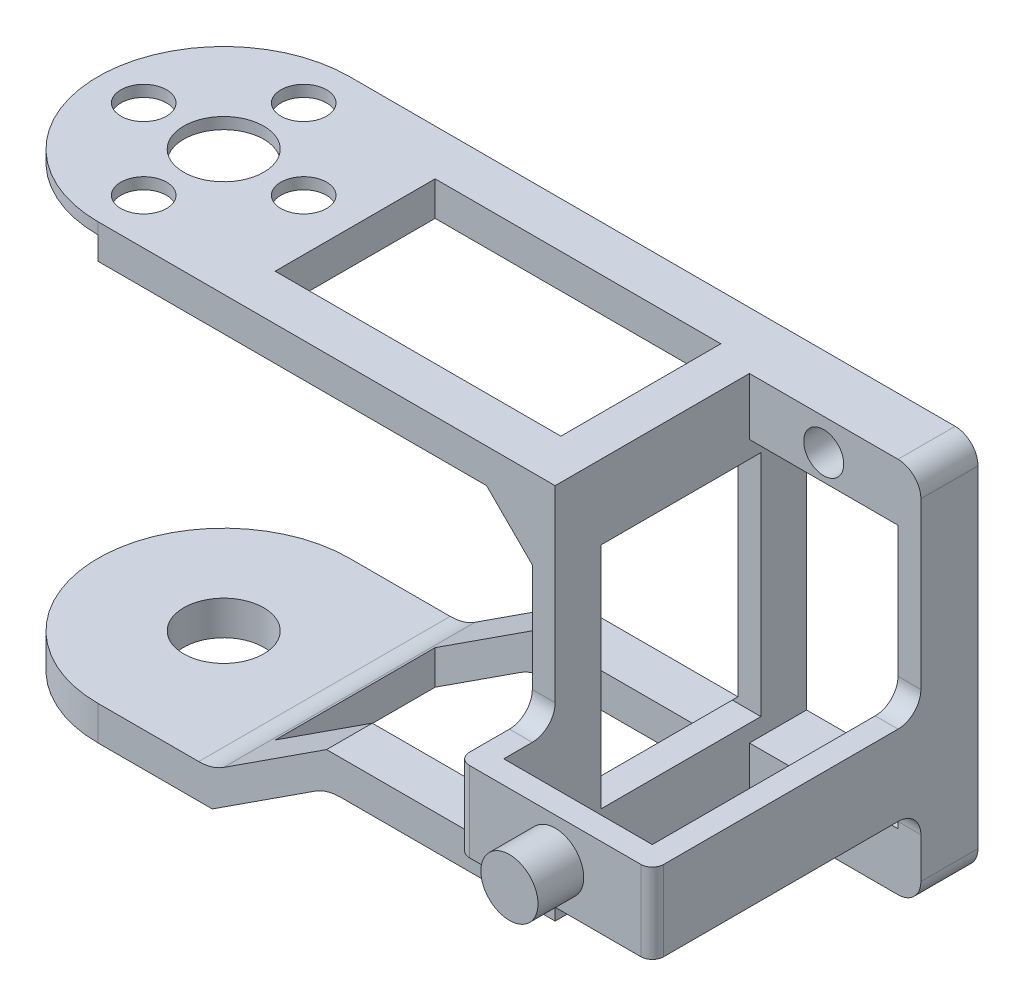
SolidWorks part; units mm, degrees
ref_plane "前视基准面" through (0, 0, 0) normal (0, 0, 1) x (1, 0, 0)
ref_plane "上视基准面" through (0, 0, 0) normal (0, 1, 0) x (1, 0, 0)
ref_plane "右视基准面" through (0, 0, 0) normal (1, 0, 0) x (0, 0, -1)
sketch "草图1" plane through (0, 0, 0) normal (0, 1, 0) x (1, 0, 0)
  line L0 (-11, 0) -> (11, 0) construction
  line L1 (0, -11) -> (0, 11) construction
  circle A1 centre (0, 0) radius 3
  circle A2 centre (-7, 0) radius 2
  circle A6 centre (0, 7) radius 2
  circle A7 centre (7, 0) radius 2
  circle A8 centre (0, -7) radius 2
  point P18 (0, 0)
  point P19 (0.1023, 0.1023)
  dimension "D1" = 7
  dimension "D2" = 6
  dimension "D3" = 4
  dimension "D4" = 4
sketch "草图2" plane through (0, 0, 0) normal (0, 1, 0) x (1, 0, 0)
  line L0 (0, -11) -> (0, 11) construction
  line L1 (0, 0) -> (67.4561, 0) construction
  line L2 (0, 11) -> (40, 11)
  line L3 (40, 11) -> (40, -11)
  line L4 (40, -11) -> (0, -11)
  arc A0 (0, -11) -> (0, 11) centre (0, 0) cw
  point P5 (40, 0)
  dimension "D1" = 11
  dimension "D4" = 40
  dimension "D3" = 11
  dimension "D2" = 11
extrude "凸台-拉伸1" add sketch "草图2" along normal blind 3
sketch "草图3" plane through (0, 0, 0) normal (0, -1, 0) x (-1, 0, 0)
  circle A0 centre (0, 0) radius 11
  dimension "D1" = 22
extrude "切除-拉伸1" cut sketch "草图3" against normal blind 2 contours A0
extrude "切除-拉伸2" cut sketch "草图1" against normal through all and the other way blind 20
ref_plane "基准面1" through (0, -33.5, 0) normal (0, -1, 0) x (-1, 0, 0)
sketch "草图4" plane through (0, -33.5, 0) normal (0, -1, 0) x (-1, 0, 0)
  line L0 (0, 0.1404) -> (0, 50000.1404) construction
  line L1 (0, 0) -> (50000, 0) construction
  line L2 (0, 11) -> (-10, 11)
  line L4 (-10, 11) -> (-10, -11)
  line L5 (-10, -11) -> (0, -11)
  line L6 (0, -11) -> (-40, -11) construction
  arc A1 (0, 11) -> (0, -11) centre (0, 0) cw
  point P0 (0, 25000.1404)
  point P1 (0, 0)
  point P2 (0, 0)
  point P3 (0, 25011.1404)
  point P8 (0, -11)
  point P9 (0, 11)
  point P17 (0, 0)
  dimension "D2" = 11
  dimension "D4" = 10
  dimension "D5" = 11
  dimension "D1" = 11
  dimension "D3" = 11
extrude "凸台-拉伸2" add sketch "草图4" along normal blind 3 separate body
sketch "草图5" plane through (0, -36.5, 0) normal (0, -1, 0) x (-1, 0, 0)
  arc A0 (0, -11) -> (0, 11) centre (0, 0) ccw construction
  circle A1 centre (0, 0) radius 3.5
  point P0 (0, 0)
  dimension "D1" = 7
extrude "切除-拉伸3" cut sketch "草图5" against normal through all
ref_plane "基准面4" through (0, -27, 0) normal (0, -1, 0) x (-1, 0, 0)
sketch "草图8" plane through (0, -27, 0) normal (0, -1, 0) x (-1, 0, 0)
  line L1 (-20, -11) -> (-40, -11)
  line L2 (-20, -11) -> (-20, 11)
  line L3 (-20, 11) -> (-40, 11)
  line L4 (-40, -11) -> (-40, 11)
  line L5 (-20, -11) -> (-40, 11) construction
  line L6 (-20, 11) -> (-40, -11) construction
  line L7 (-40, -11) -> (-40, 11) construction
  line L8 (-40, 11) -> (0, 11) construction
  line L9 (0, -11) -> (-40, -11) construction
  point P4 (-30, 0)
  dimension "D1" = 20
extrude "凸台-拉伸4" add sketch "草图8" along normal blind 3 separate body
sketch "草图10" plane through (0, 0, 0) normal (0, 0, 1) x (1, 0, 0)
  line L0 (10, -36.5) -> (20, -30)
  line L2 (20, -30) -> (20, -27)
  line L3 (20, -27) -> (10, -33.5)
  line L4 (-17.875, -33.5) -> (17.875, -33.5) construction
  line L5 (10, -36.5) -> (10, -33.5) construction
  line L6 (10, -33.5) -> (10, -36.5)
extrude "凸台-拉伸5" add sketch "草图10" along normal up to surface and the other way up to surface up to face at (30, -28.5, 11) other way up to face at (30, -28.5, -11)
ref_plane "基准面5" through (40, 0, 0) normal (1, 0, 0) x (0, 0, -1)
sketch "草图11" plane through (40, 0, 0) normal (1, 0, 0) x (0, 0, -1)
  line L0 (-11, 3) -> (11, 3) construction
  line L1 (6, 3) -> (11, 3)
  line L2 (6, 3) -> (6, -2)
  line L3 (6, -2) -> (11, -2)
  line L4 (11, 3) -> (11, -2)
  line L5 (6, 3) -> (11, -2) construction
  line L6 (6, -2) -> (11, 3) construction
  line L9 (6, -25) -> (11, -25)
  line L17 (11, 3) -> (11, 0) construction
  line L18 (6, -25) -> (6, -30)
  line L19 (6, -30) -> (11, -30)
  line L20 (11, -25) -> (11, -30)
  line L21 (6, -25) -> (11, -30) construction
  line L22 (6, -30) -> (11, -25) construction
  point P4 (8.5, 0.5)
  point P20 (8.5, -27.5)
  dimension "D1" = 5
  dimension "D2" = 0
  dimension "D3" = 5
  dimension "D4" = 23
extrude "凸台-拉伸6" add sketch "草图11" along normal blind 15 separate body
sketch "草图13" plane through (0, 3, 0) normal (0, 1, 0) x (1, 0, 0)
  line L0 (0, -11) -> (40, -11) construction
  line L1 (40, 11) -> (38, 11)
  line L2 (40, 11) -> (40, -11)
  line L3 (40, -11) -> (38, -11)
  line L4 (38, 11) -> (38, -11)
  line L5 (40, 11) -> (38, -11) construction
  line L6 (40, -11) -> (38, 11) construction
  line L7 (40, -11) -> (40, 11) construction
  line L8 (40, 11) -> (0, 11) construction
  point P4 (39, 0)
  point P5 (38.1714, 0)
  dimension "D1" = 2
extrude "凸台-拉伸7" add sketch "草图13" against normal up to surface (33 mm away) up to face at (30, -30, 0)
ref_plane "基准面7" through (0, -13.5, 0) normal (0, -1, 0) x (-1, 0, 0)
sketch "草图14" plane through (0, 0, -6) normal (0, 0, 1) x (1, 0, 0)
  line L1 (40, 3) -> (40, -2) construction
  line L2 (-2.75, -13.5) -> (2.75, -13.5) construction
  line L4 (46.5, 0.25) -> (46.5, -27.25) construction
  circle A0 centre (46.5, 0.25) radius 1.75
  circle A1 centre (46.5, -27.25) radius 1.75
  point P0 (46.5, 0.25)
  point P11 (46.5, -27.25)
  point P12 (46.5, -13.5)
  dimension "D3" = 3.5
  dimension "D4" = 3.5
  dimension "D1" = 6.5
  dimension "D2" = 27.5
sketch "草图15" plane through (0, -2, 0) normal (0, -1, 0) x (1, 0, 0)
  line L0 (55, -11) -> (40, -11) construction
  line L1 (55, -6) -> (53, -6)
  line L2 (55, -6) -> (55, -11)
  line L3 (55, -11) -> (53, -11)
  line L4 (53, -6) -> (53, -11)
  line L5 (55, -6) -> (53, -11) construction
  line L6 (55, -11) -> (53, -6) construction
  point P4 (54, -8.5)
  dimension "D1" = 2
extrude "凸台-拉伸8" add sketch "草图15" along normal up to surface (28 mm away) up to face at (38.3333, -30, -2)
extrude "切除-拉伸4" cut sketch "草图14" against normal through all
sketch "草图16" plane through (0, 0, 11) normal (0, 0, 1) x (1, 0, 0)
  line L0 (38, -27) -> (38, 0) construction
  line L1 (38, -15.45) -> (40, -15.45)
  line L2 (38, -15.45) -> (38, -22.45)
  line L3 (38, -22.45) -> (40, -22.45)
  line L4 (40, -15.45) -> (40, -22.45)
  line L5 (38, -15.45) -> (40, -22.45) construction
  line L6 (38, -22.45) -> (40, -15.45) construction
  line L9 (0, 0) -> (38, 0) construction
  line L10 (40, 3) -> (40, -30) construction
  point P4 (39, -18.95)
  point P13 (12.4702, -21.5718)
  dimension "D1" = 18.95
  dimension "D2" = 7
extrude "凸台-拉伸9" add sketch "草图16" along normal blind 6.5
sketch "草图17" plane through (40, 0, 0) normal (1, 0, 0) x (0, 0, -1)
  line L0 (-17.5, -22.45) -> (-11, -22.45) construction
  line L1 (-17.5, -15.45) -> (-15.5, -15.45)
  line L2 (-17.5, -15.45) -> (-17.5, -22.45)
  line L3 (-17.5, -22.45) -> (-15.5, -22.45)
  line L4 (-15.5, -15.45) -> (-15.5, -22.45)
  line L5 (-17.5, -15.45) -> (-15.5, -22.45) construction
  line L6 (-17.5, -22.45) -> (-15.5, -15.45) construction
  line L7 (-17.5, -22.45) -> (-17.5, -15.45) construction
  line L8 (-17.5, -15.45) -> (-11, -15.45) construction
  point P4 (-16.5, -18.95)
  dimension "D1" = 2
extrude "凸台-拉伸10" add sketch "草图17" along normal up to surface (15 mm away) up to face at (55, -13.5, -8.5)
sketch "草图18" plane through (0, 0, 15.5) normal (0, 0, -1) x (-1, 0, 0)
  line L0 (-55, -22.45) -> (-40, -22.45) construction
  line L1 (-55, -15.45) -> (-53, -15.45)
  line L2 (-55, -15.45) -> (-55, -22.45)
  line L3 (-55, -22.45) -> (-53, -22.45)
  line L4 (-53, -15.45) -> (-53, -22.45)
  line L5 (-55, -15.45) -> (-53, -22.45) construction
  line L6 (-55, -22.45) -> (-53, -15.45) construction
  point P4 (-54, -18.95)
  point P8 (-54.7423, -22.203)
  dimension "D1" = 2
extrude "凸台-拉伸11" add sketch "草图18" along normal up to surface (21.5 mm away) up to face at (48.25, 0.25, -6)
sketch "草图19" plane through (0, 0, 17.5) normal (0, 0, 1) x (1, 0, 0)
  line L0 (55, -15.45) -> (38, -15.45) construction
  line L1 (55, -15.45) -> (55, -22.45) construction
  circle A0 centre (46.5, -18.95) radius 2.5
  point P0 (46.5, -18.95)
  dimension "D3" = 5
  dimension "D1" = 3.5
  dimension "D2" = 8.5
extrude "凸台-拉伸12" add sketch "草图19" along normal blind 4
sketch "草图20" plane through (38, 0, 0) normal (-1, 0, 0) x (0, 0, 1)
  line L0 (11, -15.45) -> (11, 0) construction
  line L1 (7, -3.5) -> (-7, -3.5)
  line L2 (7, -3.5) -> (7, -23.5)
  line L3 (7, -23.5) -> (-7, -23.5)
  line L4 (-7, -3.5) -> (-7, -23.5)
  line L5 (7, -3.5) -> (-7, -23.5) construction
  line L6 (7, -23.5) -> (-7, -3.5) construction
  line L7 (-11, 0) -> (11, 0) construction
  point P4 (0, -13.5)
  dimension "D1" = 11
  dimension "D2" = 13.5
  dimension "D3" = 14
  dimension "D4" = 20
extrude "切除-拉伸5" cut sketch "草图20" against normal up to next
sketch "草图21" plane through (0, 3, 0) normal (0, 1, 0) x (1, 0, 0)
  line L0 (55, 11) -> (0, 11) construction
  line L1 (11.5, 7) -> (36.5, 7)
  line L2 (11.5, 7) -> (11.5, -7)
  line L3 (11.5, -7) -> (36.5, -7)
  line L4 (36.5, 7) -> (36.5, -7)
  line L5 (11.5, 7) -> (36.5, -7) construction
  line L6 (11.5, -7) -> (36.5, 7) construction
  circle A0 centre (0, 0) radius 3.5 construction
  point P4 (24, 0)
  dimension "D1" = 11
  dimension "D2" = 24
  dimension "D3" = 25
  dimension "D4" = 14
extrude "切除-拉伸6" cut sketch "草图21" against normal through all
chamfer "倒角1" distance 4 angle 45 2 edges at (38, -27, 0) (38, 0, 0)
fillet "圆角1" radius 4 3 edges at (10, -33.5, 0) (20, -30, -9) (20, -30, 9)
fillet "圆角2" radius 2 2 edges at (55, -30, -8.5) (55, 3, -8.5)
fillet "圆角3" radius 2 4 edges at (54, -22.45, -6) (54, -15.45, -6) (39, -22.45, 11) (39, -15.45, 11)
fillet "圆角4" radius 1 2 edges at (55, -18.95, 17.5) (38, -18.95, 17.5)
